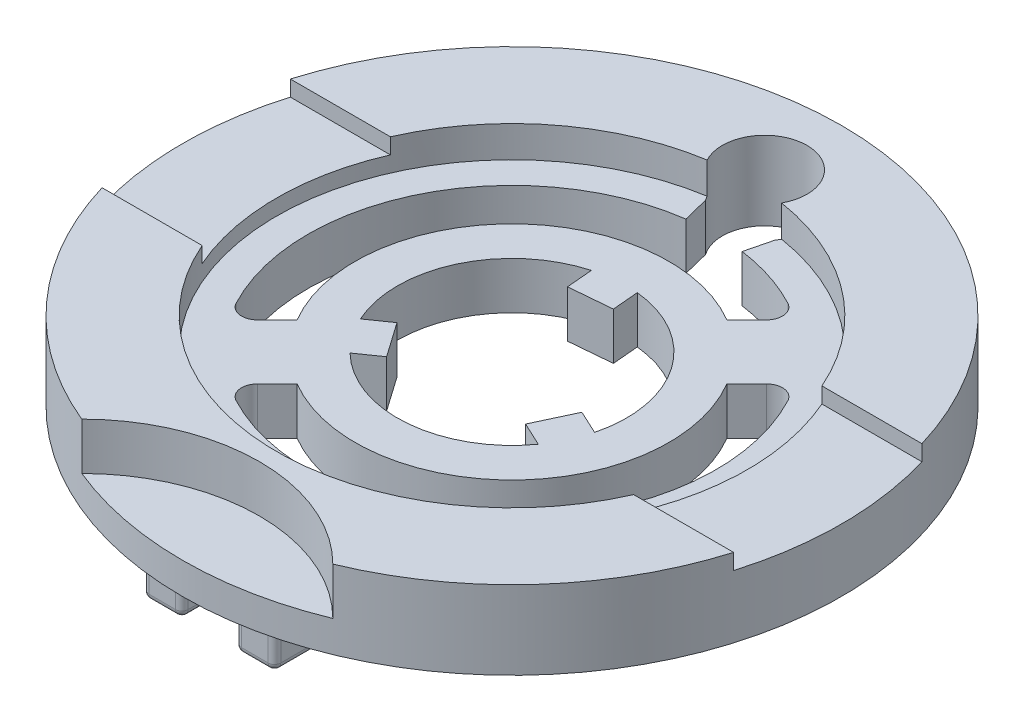
SolidWorks part; units mm, degrees
ref_plane "Front Plane" through (0, 0, 0) normal (0, 0, 1) x (1, 0, 0)
ref_plane "Top Plane" through (0, 0, 0) normal (0, 1, 0) x (1, 0, 0)
ref_plane "Right Plane" through (0, 0, 0) normal (1, 0, 0) x (0, 0, -1)
sketch "Sketch2" plane through (0, 0, 0) normal (0, 1, 0) x (1, 0, 0)
  circle A0 centre (0, 0) radius 10.5
  circle A1 centre (0, 0) radius 7.5
  circle A2 centre (0, 0) radius 6.5
  dimension "D1" = 15
  dimension "D2" = 21
  dimension "D3" = 1
extrude "Boss-Extrude1" add sketch "Sketch2" along normal blind 2.5 contours A0 A1 region at (-10.203, 0, 0)
extrude "Boss-Extrude2" add sketch "Sketch2<3>" along normal blind 1.5 contours A1 A2 region at (-7.2879, 0, 0)
sketch "Sketch2<3>" plane through (0, 0, 0) normal (0, 1, 0) x (1, 0, 0) same geometry as "Sketch2"
sketch "Sketch3" plane through (0, 2.5, 0) normal (0, 1, 0) x (1, 0, 0)
  line L1 (-15, -3) -> (15, -3)
  line L2 (-15, -3) -> (-15, 3)
  line L3 (-15, 3) -> (15, 3)
  line L4 (15, -3) -> (15, 3)
  line L5 (-15, -3) -> (15, 3) construction
  line L6 (-15, 3) -> (15, -3) construction
  point P0 (0, 0)
  dimension "D1" = 6
  dimension "D2" = 30
extrude "Cut-Extrude1" cut sketch "Sketch3" against normal blind 0.5
sketch "Sketch4" plane through (0, 2.5, 0) normal (0, 1, 0) x (1, 0, 0)
  line L0 (4, -9.7082) -> (-4, -9.7082)
  circle A0 centre (0, -13.7035) radius 5.6535
  arc A1 (-10.0623, -3) -> (10.0623, -3) centre (0, 0) ccw construction
  circle A6 centre (0, 0) radius 6.5 construction
  arc M3 (-10.0623, -3) -> (10.0623, -3) centre (0, 0) ccw
  dimension "D1" = 1.55
  dimension "D2" = 8
extrude "Cut-Extrude2" cut sketch "Sketch4" against normal blind 1.5 contours L0 A0 | L0 M3 region at (0, 2.5, 10.026) region at (0, 2.5, 9.0358)
sketch "Sketch5" plane through (0, 0, 0) normal (0, 1, 0) x (1, 0, 0)
  line L0 (3.6265, 5.3943) -> (2.5394, 4.3071)
  line L1 (5.3943, 3.6265) -> (4.3071, 2.5394)
  line L2 (-5.3943, -3.6265) -> (-4.3071, -2.5394)
  line L3 (-3.6265, -5.3943) -> (-2.5394, -4.3071)
  line L4 (0, 0) -> (9.2382, 9.2382) construction
  line L5 (0, 0) -> (14.7739, 0) construction
  line L6 (0.3598, 3.6322) -> (0.4328, 2.7984)
  line L7 (0.4328, 2.7984) -> (-0.9121, 2.6807)
  line L8 (-0.9121, 2.6807) -> (-0.9851, 3.5146)
  line L9 (0, 0) -> (-0.2397, 2.7395) construction
  line L10 (2.7776, -0.5504) -> (3.5362, -0.9042)
  line L11 (2.2071, -1.774) -> (2.7776, -0.5504)
  line L12 (2.9657, -2.1277) -> (2.2071, -1.774)
  line L13 (-1.8655, -2.1303) -> (-2.5512, -2.6104)
  line L14 (-2.6398, -1.0244) -> (-1.8655, -2.1303)
  line L15 (-3.3255, -1.5045) -> (-2.6398, -1.0244)
  circle A0 centre (0, 0) radius 5
  circle A1 centre (0, 0) radius 3.65
  circle A2 centre (0, 0) radius 6.5 construction
  circle A3 centre (0, 0) radius 6.5
  point P31 (0, 0)
  dimension "D4" = 1.35
  dimension "D5" = 10
  dimension "D1" = 45
  dimension "D2" = 2.5
  dimension "D3" = 2.5
  dimension "D6" = 1.25
  dimension "D7" = 1.35
  dimension "D8" = 0.9
  dimension "D10" = 95
  dimension "D9" = 3
extrude "Boss-Extrude3" add sketch "Sketch5" along normal up to surface (1.5 mm away) contours A0 A1 | L2 A3 L3 A0 | L12 A1 L10 L11 | L15 A1 L13 L14 | L6 A1 L8 L7 | L1 A3 L0 A0 region at (4.0328, 0, -4.0328) region at (3.4355, 0, -3.4355) region at (-4.0328, 0, 4.0328) region at (-0.278, 0, -3.1776) region at (2.8909, 0, 1.348) region at (-2.6129, 0, 1.8296) up to face at (0, 1.5, 6.5)
fillet "Fillet1" radius 0.5 4 edges at (-5.3943, 0.75, 3.6265) (-3.6265, 0.75, 5.3943) (3.6265, 0.75, -5.3943) (5.3943, 0.75, -3.6265)
sketch "Sketch6" plane through (0, 2.5, 0) normal (0, 1, 0) x (1, 0, 0)
  line L0 (-0.8959, 6.438) -> (-1.1041, 7.2732)
  line L1 (0.8959, 6.438) -> (1.1041, 7.2732)
  line L2 (0, 8.05) -> (0, 0) construction
  circle A0 centre (0, 8.05) radius 1.35
  arc A2 (10.0623, 3) -> (-10.0623, 3) centre (0, 0) ccw construction
  arc A3 (3.0558, 5.7369) -> (-5.7369, -3.0558) centre (0, 0) ccw construction
  circle A4 centre (0, 0) radius 6.5
  point P12 (-1, 6.8556)
  point P15 (1, 6.8556)
  arc M7 (-6.8739, 3) -> (6.8739, 3) centre (0, 0) cw
  dimension "D1" = 2.7
  dimension "D2" = 1.1
  dimension "D3" = 2
  dimension "D4" = 1
  dimension "D5" = 14
  dimension "D6" = 14
extrude "Cut-Extrude3" cut sketch "Sketch6" against normal blind 10 contours A0 M7 | L2 A0 M7 | L2 A0 M7 | L2 A0 L0 A4 | A0 L2 A4 L1 region at (-0.6104, 2.5, -6.7009) region at (-0.4635, 2.5, -7.1524) region at (0.6104, 2.5, -6.7009) region at (0, 2.5, -8.3245) region at (0.4635, 2.5, -7.1524)
sketch "Sketch7" plane through (0, 0, 0) normal (0, -1, 0) x (1, 0, 0)
  line L0 (0, 0) -> (0, 11.4149) construction
  line L1 (1.05, 6.6679) -> (1.9, 6.6679)
  line L2 (0.85, 6.8679) -> (0.85, 9.4679)
  line L3 (1.05, 9.6679) -> (1.9, 9.6679)
  line L4 (2.1, 6.8679) -> (2.1, 9.4679)
  line L5 (-2.1, 6.8679) -> (-2.1, 9.4679)
  line L6 (-1.05, 9.6679) -> (-1.9, 9.6679)
  line L7 (-0.85, 6.8679) -> (-0.85, 9.4679)
  line L8 (-1.05, 6.6679) -> (-1.9, 6.6679)
  line L9 (2.1, 9.6679) -> (0.85, 6.6679) construction
  arc A2 (1.9, 6.6679) -> (2.1, 6.8679) centre (1.9, 6.8679) ccw
  arc A3 (1.05, 6.6679) -> (0.85, 6.8679) centre (1.05, 6.8679) cw
  arc A4 (1.9, 9.6679) -> (2.1, 9.4679) centre (1.9, 9.4679) cw
  arc A5 (0.85, 9.4679) -> (1.05, 9.6679) centre (1.05, 9.4679) cw
  arc A6 (-1.05, 9.6679) -> (-0.85, 9.4679) centre (-1.05, 9.4679) cw
  arc A7 (-0.85, 6.8679) -> (-1.05, 6.6679) centre (-1.05, 6.8679) cw
  arc A8 (-1.9, 6.6679) -> (-2.1, 6.8679) centre (-1.9, 6.8679) cw
  arc A9 (-2.1, 9.4679) -> (-1.9, 9.6679) centre (-1.9, 9.4679) cw
  point P11 (1.475, 8.1679)
  point P14 (2.1, 6.6679)
  point P23 (0.85, 9.6679)
  point P26 (-0.85, 9.6679)
  point P29 (-0.85, 6.6679)
  point P32 (-2.1, 6.6679)
  point P35 (-2.1, 9.6679)
  dimension "D4" = 8.3
  dimension "D5" = 0.2
  dimension "D1" = 3
  dimension "D2" = 1.25
  dimension "D3" = 4.2
extrude "Boss-Extrude4" add sketch "Sketch7" along normal blind 1.5
fillet "Fillet2" radius 0.2 16 edges at (0.9086, -1.5, 9.6093) (1.475, -1.5, 9.6679) (2.0414, -1.5, 9.6093) (2.1, -1.5, 8.1679) (2.0414, -1.5, 6.7265) (1.475, -1.5, 6.6679) (0.9086, -1.5, 6.7265) (-0.9086, -1.5, 6.7265) (-1.475, -1.5, 6.6679) (-2.0414, -1.5, 6.7265) (-2.1, -1.5, 8.1679) (-2.0414, -1.5, 9.6093) (-1.475, -1.5, 9.6679) (-0.9086, -1.5, 9.6093) (0.85, -1.5, 8.1679) (-0.85, -1.5, 8.1679)
